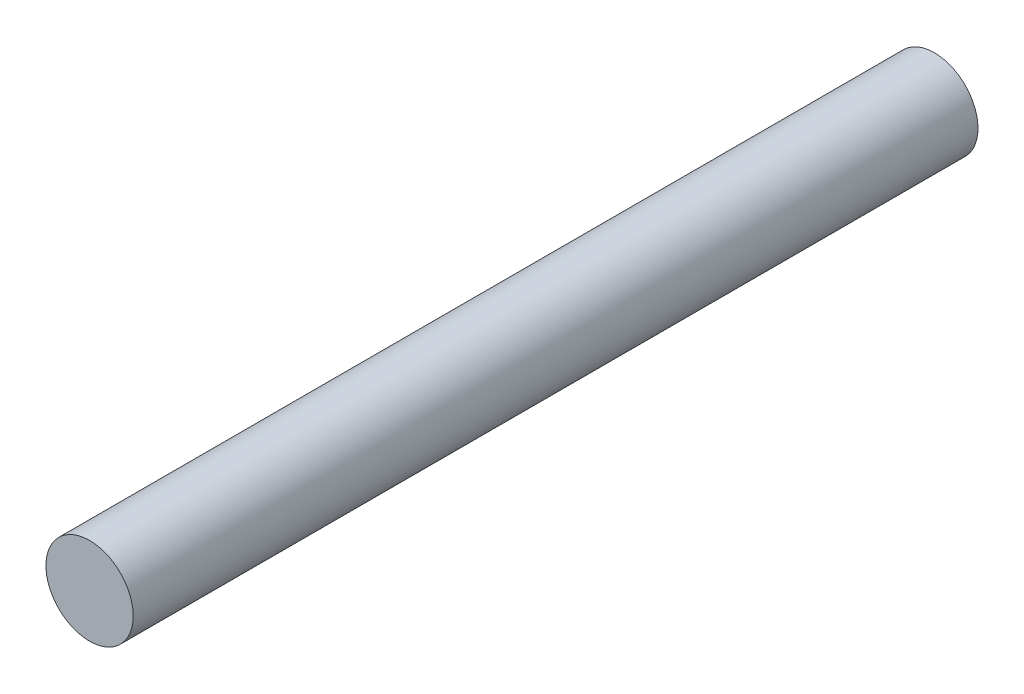
SolidWorks part; units mm, degrees
ref_plane "前视基准面" through (0, 0, 0) normal (0, 0, 1) x (1, 0, 0)
ref_plane "上视基准面" through (0, 0, 0) normal (0, 1, 0) x (1, 0, 0)
ref_plane "右视基准面" through (0, 0, 0) normal (1, 0, 0) x (0, 0, -1)
sketch "草图1" plane through (0, 0, 0) normal (0, 0, 1) x (1, 0, 0)
  circle A0 centre (0, 0) radius 3.1
extrude "凸台-拉伸1" add sketch "草图1" along normal blind 60
